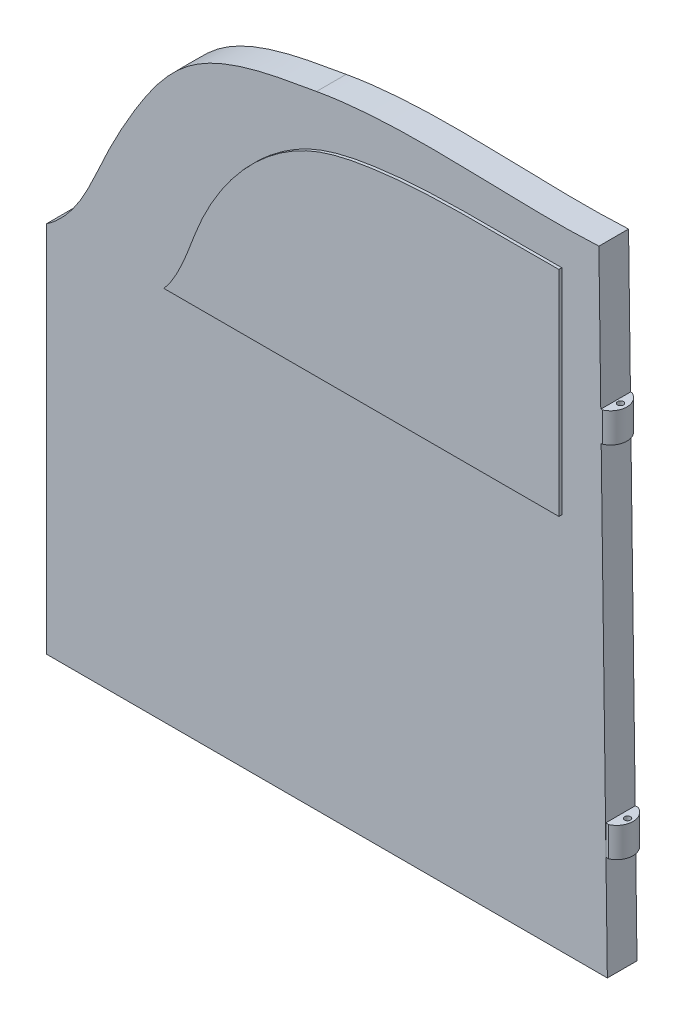
SolidWorks part; units mm, degrees
ref_plane "Front Plane" through (0, 0, 0) normal (0, 0, 1) x (1, 0, 0)
ref_plane "Top Plane" through (0, 0, 0) normal (0, 1, 0) x (1, 0, 0)
ref_plane "Right Plane" through (0, 0, 0) normal (1, 0, 0) x (0, 0, -1)
sketch "Sketch1" plane through (0, 0, 0) normal (0, 0, 1) x (1, 0, 0)
  line L0 (-221.4454, 149.8652) -> (535.2213, 149.8652) construction
  line L1 (186.2801, 212.2169) -> (189.1274, 0)
  line L2 (189.1274, 0) -> (0, 0)
  line L3 (0, 0) -> (0, 125.5767)
  spline S0 degree 3 poles (0, 125.5767) (10.557, 132.8376) (17.0982, 150.7511) (30.5385, 175.7634) (49.3522, 203.0408) (76.8679, 207.297) (91.098, 209.7763) knots 0 0 0 0 0.275246 0.426572 0.655829 1 1 1 1
  spline S1 degree 3 poles (91.098, 209.7763) (122.5651, 215.3748) (154.601, 210.5155) (186.2801, 212.2169) knots 0 0 0 0 1 1 1 1
sketch "Sketch2" plane through (0, 0, 0) normal (0, 0, 1) x (1, 0, 0)
extrude "Boss-Extrude1" add sketch "Sketch1" along normal blind 10
sketch "Sketch3" plane through (0, 0, 10) normal (0, 0, 1) x (1, 0, 0)
  line L0 (40.6919, 127.5652) -> (173.8037, 127.5652)
  line L1 (173.8037, 127.5652) -> (173.8037, 199.6793)
  spline S0 degree 3 poles (40.6919, 127.5652) (46.7713, 134.9333) (53.3691, 161.7045) (78.4575, 191.2123) (124.3175, 201.0388) (152.2649, 199.3628) (173.8037, 199.6793) knots 0 0 0 0 0.165618 0.500502 0.611599 1 1 1 1
extrude "Boss-Extrude2" add sketch "Sketch3" along normal blind 1 and the other way blind 11
ref_plane "Plane1" through (0, 100, 0) normal (0, -1, 0) x (-1, 0, 0)
ref_plane "Plane2" through (32.1075, 0.4308, 0) normal (0.9999, 0.0134, 0) x (0, 0, -1)
ref_plane "Plane3" through (0, 40, 0) normal (0, -1, 0) x (-1, 0, 0)
ref_plane "Plane4" through (0, 160, 0) normal (0, -1, 0) x (-1, 0, 0)
sketch "Sketch16" plane through (189.0934, 2.5371, 0) normal (0.9999, 0.0134, 0) x (0, 0, -1)
  line L0 (-10, 38.6394) -> (0, 38.6394) construction
  line L1 (-10, -2.5373) -> (-10, 209.6987) construction
  line L2 (0, -2.5373) -> (0, 209.6987) construction
  line L3 (-10, 158.0625) -> (0, 158.0625) construction
sketch "Sketch17" plane through (0, 40, 0) normal (0, -1, 0) x (-1, 0, 0)
  line L0 (-188.575, 0) -> (-189.575, 0)
  line L1 (-188.575, -10) -> (-188.575, 0) construction
  line L2 (-188.575, -9.9807) -> (-189.575, -9.9807)
  line L3 (-188.575, 0) -> (-188.575, -9.9807)
  arc A1 (-189.575, -9.9807) -> (-189.575, 0) centre (-187.2628, -4.9904) cw
  dimension "D1" = 1
extrude "Boss-Extrude3" add sketch "Sketch17" along normal blind 5 and the other way blind 5 contours L2 A1 L0 L3
sketch "Sketch18" plane through (0, 160, 0) normal (0, -1, 0) x (-1, 0, 0)
  line L0 (-186.9729, -10) -> (-187.4729, -10)
  line L1 (-186.9729, -10) -> (-186.9729, 0) construction
  line L2 (-186.9729, 0) -> (-187.4729, 0)
  line L3 (0, 0) -> (-189.1274, 0) construction
  line L4 (-188.6578, 0) -> (-189.575, 0) construction
  line L5 (-186.9729, 0) -> (-186.9729, -10)
  arc A1 (-187.4729, -10) -> (-187.4729, 0) centre (-185.2471, -5) cw
  dimension "D2" = 5.473
  dimension "D1" = 0.5
extrude "Boss-Extrude4" add sketch "Sketch18" along normal blind 5 and the other way blind 5 contours L2 A1 L0 L5
sketch "Sketch19" plane through (0, 155, 0) normal (0, -1, 0) x (1, 0, 0)
  line L0 (188.575, 10) -> (188.575, 0) construction
  circle A2 centre (188.575, 5) radius 1
extrude "Cut-Extrude3" cut sketch "Sketch19" against normal blind 10 contours A2
sketch "Sketch24" plane through (0, 35, 0) normal (0, -1, 0) x (1, 0, 0)
  circle A1 centre (190.9451, 4.9952) radius 1
extrude "Cut-Extrude4" cut sketch "Sketch24" against normal blind 10 contours A1
ref_plane "Plane12" through (30, 0, 0) normal (-1, 0, 0) x (0, 0, 1)
sketch "Sketch27" plane through (30, 0, 0) normal (-1, 0, 0) x (0, 0, 1)
  line L0 (-12.0323, 100) -> (0, 100)
  line L3 (0, 125.5767) -> (0, 0) construction
  arc A0 (0, 112.6572) -> (-12.0323, 100) centre (0.3125, 100.3125) ccw
ref_plane "Plane13" through (0, 100, 0) normal (0, 1, 0) x (1, 0, 0)
sketch "Sketch30" plane through (0, 100, 0) normal (0, 1, 0) x (1, 0, 0)
  line L0 (17.9677, 0) -> (42.0323, 0)
  line L1 (91.098, 0) -> (0, 0) construction
  line L2 (30, 12.0323) -> (30, 0) construction
  arc A0 (17.9677, 0) -> (42.0323, 0) centre (30, 0) cw
revolve "Revolve2" add sketch "Sketch30" angle 90 about L0
sketch "Sketch31" plane through (0, 100, 0) normal (0, -1, 0) x (1, 0, 0)
  line L0 (17.9677, 0) -> (42.0323, 0) construction
  line L1 (20.0035, 0) -> (39.8046, 0)
  arc A0 (20.0035, 0) -> (39.8046, 0) centre (29.904, 0) ccw
ref_plane "Plane10" through (0, 45, 0) normal (0, 1, 0) x (1, 0, 0)
ref_plane "Plane14" through (42.0323, 100, 0) normal (1, 0, 0) x (0, 0, -1)
revolve "Cut-Revolve4" cut sketch "Sketch31" angle 80 about L1
